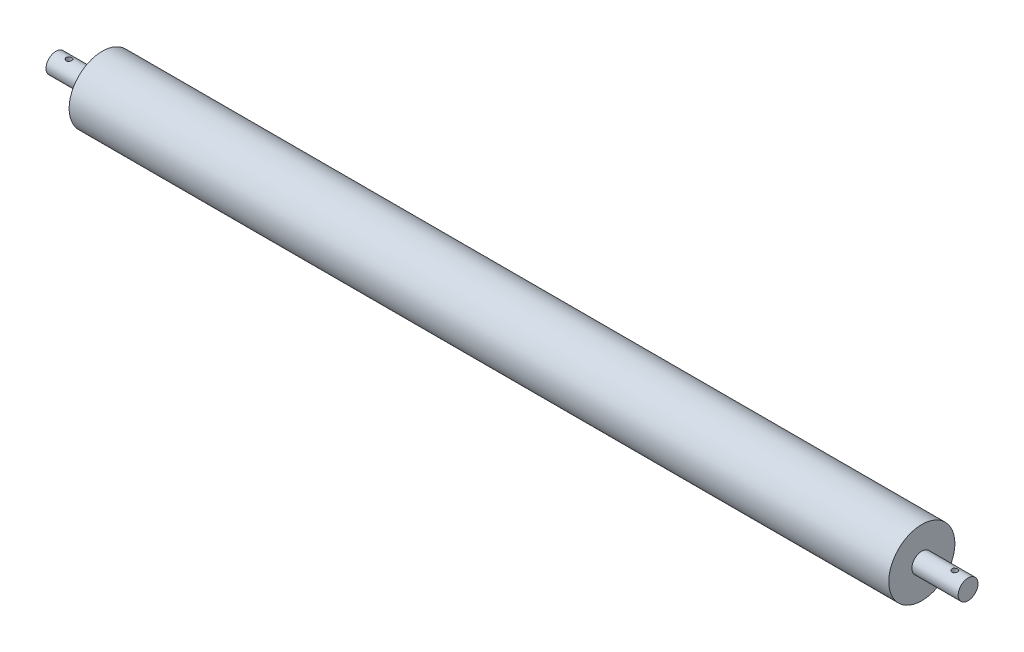
SolidWorks part; units mm, degrees
ref_plane "前视基准面" through (0, 0, 0) normal (0, 0, 1) x (1, 0, 0)
ref_plane "上视基准面" through (0, 0, 0) normal (0, 1, 0) x (1, 0, 0)
ref_plane "右视基准面" through (0, 0, 0) normal (1, 0, 0) x (0, 0, -1)
sketch "草图1" plane through (0, 0, 0) normal (0, 0, 1) x (1, 0, 0)
  line L0 (-230.7094, 0) -> (459.7941, 0) construction
  line L1 (0, 215.5466) -> (0, -189.8195) construction
  line L2 (-310, 25) -> (310, 25)
  line L8 (-310, 25) -> (-310, 7.5)
  line L9 (-345, 0) -> (345, 0)
  line L10 (-345, 0) -> (-345, 7.5)
  line L11 (-345, 7.5) -> (-310, 7.5)
  line L14 (345, 0) -> (345, 7.5)
  line L15 (345, 7.5) -> (310, 7.5)
  line L16 (310, 25) -> (310, 7.5)
  point P3 (-310, 16.25)
  point P13 (-322.5, 0)
  point P17 (0, 25)
  point P18 (-322.5, 1.1904)
  dimension "D1" = 7.5
  dimension "D2" = 35
  dimension "D3" = 25
  dimension "D4" = 620
revolve "旋转1" add sketch "草图1" angle 360 about L9
ref_plane "基准面1" through (0, -7.5, 0) normal (0, -1, 0) x (-1, 0, 0)
hole_wizard "M5 螺纹孔1" positions "草图2" profile "草图3" tap size "M5" standard "GB"
sketch "草图2" plane through (0, -7.5, 0) normal (0, -1, 0) x (-1, 0, 0)
  line L0 (345, -7.5) -> (345, 7.5) construction
  line L1 (345, 0) -> (317.0408, 0) construction
  point P2 (335, 0)
  dimension "D1" = 10
  dimension "D2" = 0
sketch "草图3" plane through (-335, -7.5, 0) normal (1, 0, 0) x (0, 0, -1)
  line L0 (0, 0) -> (0, 51.2618)
  line L1 (0, 51.2618) -> (2.1, 50)
  line L2 (2.1, 50) -> (2.1, 0)
  line L5 (2.1, 0) -> (0, 0)
  line L10 (0, 51.2618) -> (-2.1, 50) construction
  line L11 (0, -6.35) -> (0, 107.95) construction
  dimension "螺纹孔钻头直径" = 4.2
  dimension "螺纹孔钻头深度" = 50
  dimension "导头角度" = 118
cosmetic thread "孔螺蚊线1"
mirror "镜向1" about plane through (0, 0, 0) normal (1, 0, 0) of "M5 螺纹孔1"
cosmetic thread "孔螺蚊线2"
